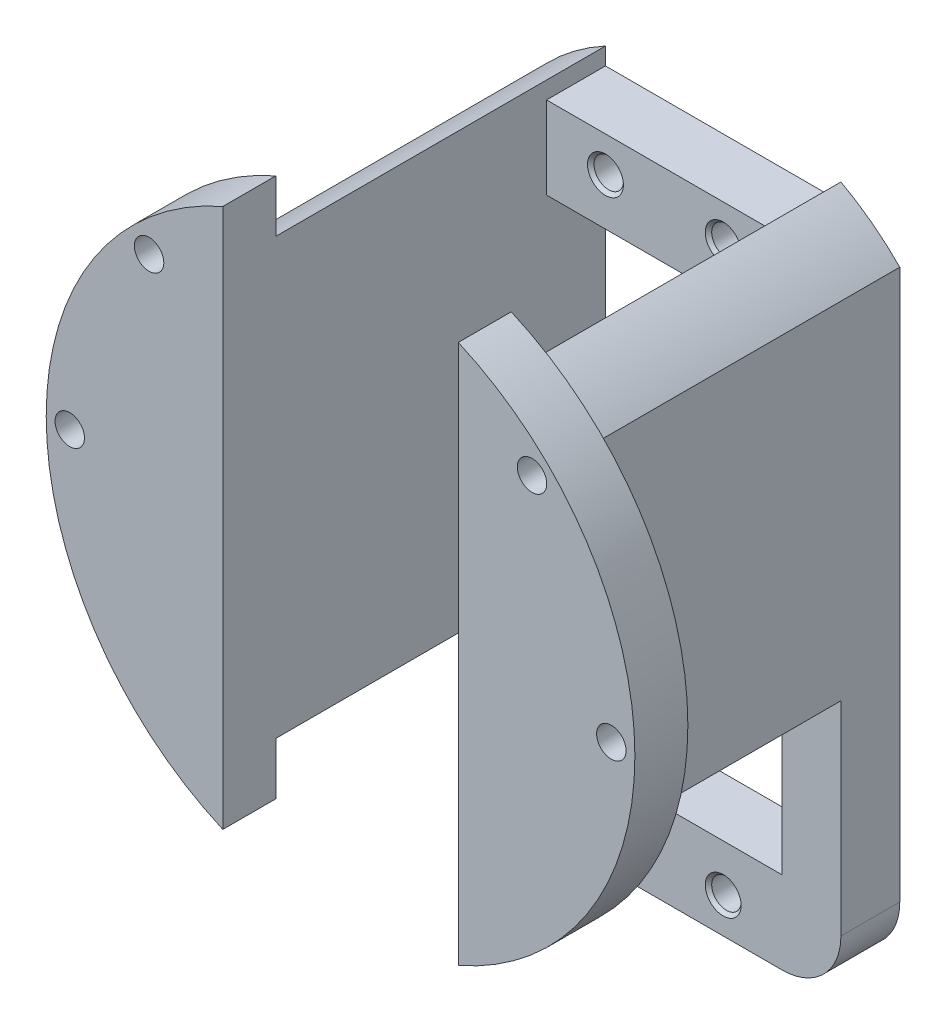
SolidWorks part; units mm, degrees
material "ПК/АБС"
ref_plane "Спереди" through (0, 0, 0) normal (0, 0, 1) x (1, 0, 0)
ref_plane "Сверху" through (0, 0, 0) normal (0, 1, 0) x (1, 0, 0)
ref_plane "Справа" through (0, 0, 0) normal (1, 0, 0) x (0, 0, -1)
sketch "Эскиз1" plane through (0, 0, 0) normal (0, 0, 1) x (1, 0, 0)
  line L0 (0, 0) -> (0, 23258.0729) construction
  line L1 (0, 0) -> (23258.0729, 0) construction
  line L2 (-10, 10) -> (10, 10)
  line L3 (10, 10) -> (10, -30)
  line L4 (10, -30) -> (-10, -30)
  line L5 (-10, -30) -> (-10, 10)
  line L6 (-15, 17) -> (15, 17)
  line L7 (15, 17) -> (15, -37)
  line L8 (15, -37) -> (-15, -37)
  line L9 (-15, -37) -> (-15, 17)
  point P7 (0, -30)
  dimension "D1" = 20
  dimension "D2" = 40
  dimension "D3" = 10
  dimension "D4" = 7
  dimension "D5" = 7
  dimension "D6" = 5
  dimension "D7" = 5
extrude "Бобышка-Вытянуть1" add sketch "Эскиз1" along normal blind 5
sketch "Эскиз2" plane through (0, 0, 0) normal (0, 0, 1) x (1, 0, 0)
  line L0 (10, -18.4662) -> (10, 18.4662)
  line L1 (10, -30) -> (10, 10) construction
  line L2 (-10, -18.4662) -> (-10, 18.4662)
  line L3 (-10, 10) -> (-10, -30) construction
  line L4 (-15, -14.6969) -> (-15, 14.6969)
  line L5 (-15, 17) -> (-15, -37) construction
  line L6 (15, 14.6969) -> (15, -14.6969)
  line L7 (15, -37) -> (15, 17) construction
  arc A0 (-10, 18.4662) -> (-15, 14.6969) centre (0, 0) ccw
  arc A1 (10, -18.4662) -> (15, -14.6969) centre (0, 0) ccw
  arc A2 (-15, -14.6969) -> (-10, -18.4662) centre (0, 0) ccw
  arc A3 (15, 14.6969) -> (10, 18.4662) centre (0, 0) ccw
  dimension "D1" = 42
extrude "Бобышка-Вытянуть2" add sketch "Эскиз2" along normal blind 28
sketch "Эскиз3" plane through (0, 0, 28) normal (0, 0, 1) x (1, 0, 0)
  line L0 (-21, 0) -> (21, 0) construction
  line L1 (-15, -21.3826) -> (-15, -50021.3826) construction
  line L2 (-15, -14.6969) -> (-15, -37) construction
  line L3 (15, -21.1704) -> (15, -50021.1704) construction
  line L4 (15, -37) -> (15, -14.6969) construction
  line L5 (-15, -14.6969) -> (-15, -37)
  line L6 (-15, -37) -> (15, -37)
  line L7 (15, -37) -> (15, -14.6969)
  circle A0 centre (0, 0) radius 21 construction
  arc A10 (-15, -14.6969) -> (15, -14.6969) centre (0, 0) cw
  point P9 (-15, -25.8485)
  point P16 (15, -25.8485)
  point P25 (0, 0)
  dimension "D2" = 42
extrude "Вырез-Вытянуть1" cut sketch "Эскиз3" against normal through all flip side to cut
fillet "Скругление1" radius 5 2 edges at (-15, -37, 2.5) (15, -37, 2.5)
sketch "Эскиз7" plane through (0, 0, 28) normal (0, 0, 1) x (1, 0, 0)
  line L2 (-10, -22.9129) -> (-10, 22.9129)
  line L3 (10, -22.9129) -> (10, 22.9129)
  line L4 (10, -30) -> (10, -18.4662) construction
  line L5 (-10, -18.4662) -> (-10, -30) construction
  arc A2 (-10, 22.9129) -> (-10, -22.9129) centre (0, 0) ccw
  arc A3 (10, -22.9129) -> (10, 22.9129) centre (0, 0) ccw
  point P8 (13.3282, -21.1509)
  point P11 (10, -22.8718)
  point P16 (-4.2578, -24.6347)
  point P17 (-10, -22.9129)
  dimension "D1" = 50
extrude "Бобышка-Вытянуть3" add sketch "Эскиз7" along normal blind 4.5
hole_wizard "Отверстие обработанное метчиком M3x0.51" positions "Эскиз4" profile "Эскиз5" tap size "M3x0.5" standard "HASCO Metric" end condition through all
sketch "Эскиз4" plane through (0, 0, 5) normal (0, 0, 1) x (1, 0, 0)
  line L0 (0, 0) -> (0, 50000) construction
  line L1 (0, -10) -> (-50000, -10) construction
  line L2 (10, 10) -> (-10, 10) construction
  line L4 (0, 14) -> (-50000, 14) construction
  line L5 (-5, -10) -> (-5, 49990) construction
  point P0 (-5, 14)
  dimension "D1" = 20
  dimension "D2" = 24
  dimension "D3" = 5
sketch "Эскиз5" plane through (-5, 14, 5) normal (1, 0, 0) x (0, -1, 0)
  line L0 (0, 0) -> (0, 5)
  line L1 (0, 5) -> (1.25, 5)
  line L2 (1.25, 5) -> (1.25, 0.275)
  line L3 (1.25, 0.275) -> (1.525, 0)
  line L5 (1.525, 0) -> (0, 0)
  line L6 (-1.25, 0.275) -> (-1.525, 0) construction
  line L11 (0, -6.35) -> (0, 107.95) construction
  dimension "Диаметр проходного сверла" = 2.5
  dimension "Глубина проходного сверла" = 5
  dimension "Диаметр передней зенковки" = 3.05
  dimension "Угол передней зенковки" = 90
cosmetic thread "Отверстие резьбы1" parameters "D2"=3
pattern_linear "Линейный массив1" count 2 spacing 10 along (1, 0, 0) count 2 spacing 48 along (0, -1, 0) of "Отверстие обработанное метчиком M3x0.51"
hole_wizard "Отверстие1" positions "Эскиз8" profile "Эскиз9" legacy end condition through all
sketch "Эскиз8" plane through (0, 0, 32.5) normal (0, 0, 1) x (1, 0, 0)
  line L0 (-23, 0) -> (23, 0) construction
  circle A0 centre (0, 0) radius 23 construction
  point P0 (-23, 0)
  point P11 (0, 0)
  point P12 (-23, 0)
  dimension "D1" = 46
sketch "Эскиз9" plane through (-23, 0, 32.5) normal (1, 0, 0) x (0, -1, 0)
  line L0 (0, 0) -> (0, 32.5)
  line L1 (0, 32.5) -> (1.25, 32.5)
  line L2 (1.25, 32.5) -> (1.25, 0)
  line L3 (1.25, 0) -> (0, 0)
  line L4 (0, 110) -> (0, -10) construction
  dimension "Диаметр" = 2.5
  dimension "Глубина" = 32.5
pattern_circular "Круговой массив1" count 8 over 360 about axis through (0, 0, 32.5) along (0, 0, 1) skipping 1, 2, 3, 6 of "Отверстие1"
